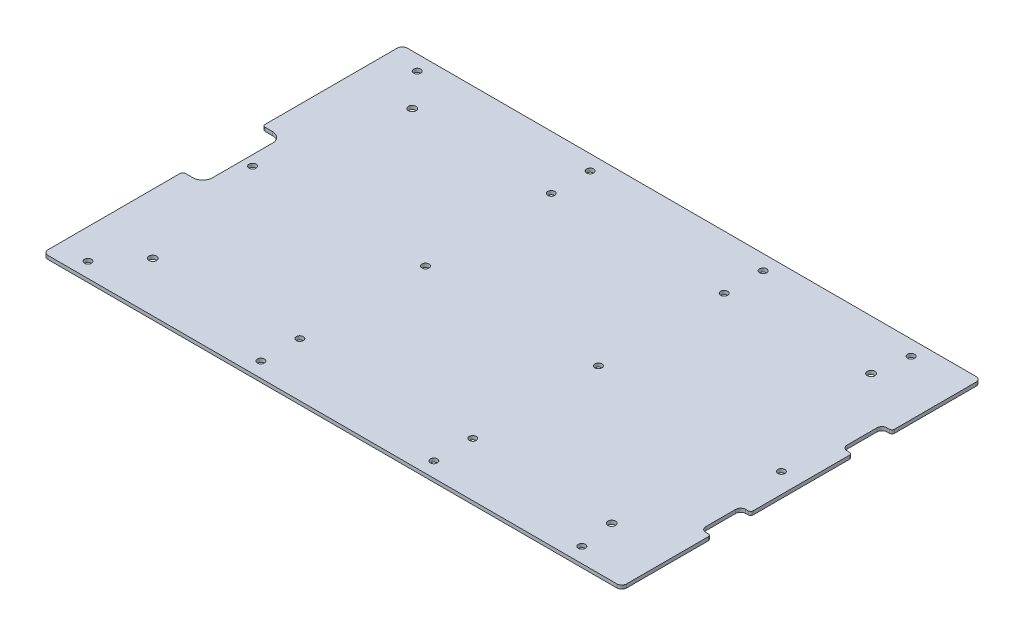
SolidWorks part; units mm, degrees
material "1060 Alloy"
ref_plane "Front" through (0, 0, 0) normal (0, 0, 1) x (1, 0, 0)
ref_plane "Top" through (0, 0, 0) normal (0, 1, 0) x (1, 0, 0)
ref_plane "Right" through (0, 0, 0) normal (1, 0, 0) x (0, 0, -1)
sketch "Sketch1" plane through (0, 0, 0) normal (0, 1, 0) x (1, 0, 0)
  line L0 (-55.0333, 0) -> (-165.1, 0) construction
  line L1 (-180.975, 114.3) -> (180.975, 114.3)
  line L2 (-184.15, 111.125) -> (-184.15, -111.125)
  line L3 (-180.975, -114.3) -> (180.975, -114.3)
  line L4 (184.15, 111.125) -> (184.15, -111.125)
  line L5 (-184.15, 114.3) -> (184.15, -114.3) construction
  line L6 (-184.15, -114.3) -> (184.15, 114.3) construction
  line L7 (-165.1, -104.775) -> (165.1, -104.775) construction
  line L8 (-165.1, -104.775) -> (-165.1, 104.775) construction
  line L9 (-165.1, 104.775) -> (165.1, 104.775) construction
  line L10 (165.1, -104.775) -> (165.1, 104.775) construction
  line L11 (-165.1, -104.775) -> (165.1, 104.775) construction
  line L12 (-165.1, 104.775) -> (165.1, -104.775) construction
  line L13 (-55.0333, -104.775) -> (55.0333, -104.775) construction
  line L14 (-55.0333, -104.775) -> (-55.0333, 104.775) construction
  line L15 (-55.0333, 104.775) -> (55.0333, 104.775) construction
  line L16 (55.0333, -104.775) -> (55.0333, 104.775) construction
  line L17 (-55.0333, -104.775) -> (55.0333, 104.775) construction
  line L18 (-55.0333, 104.775) -> (55.0333, -104.775) construction
  line L19 (55.0333, 0) -> (165.1, 0) construction
  line L20 (-55.0333, 0) -> (55.0333, 0) construction
  line L31 (-55.0291, 80.01) -> (55.0291, 80.01) construction
  line L32 (149.225, -104.775) -> (149.225, 104.775) construction
  line L33 (-55.0291, 80.01) -> (-55.0291, -80.01) construction
  line L34 (-55.0291, -80.01) -> (55.0291, -80.01) construction
  line L35 (55.0291, 80.01) -> (55.0291, -80.01) construction
  line L36 (-55.0291, 80.01) -> (55.0291, -80.01) construction
  line L37 (-55.0291, -80.01) -> (55.0291, 80.01) construction
  circle A0 centre (-165.1, 104.775) radius 2.2479
  circle A1 centre (-55.0333, 104.775) radius 2.2479
  circle A2 centre (55.0333, 104.775) radius 2.2479
  circle A3 centre (165.1, 104.775) radius 2.2479 construction
  circle A4 centre (165.1, -104.775) radius 2.2479 construction
  circle A5 centre (55.0333, -104.775) radius 2.2479
  circle A6 centre (-55.0333, -104.775) radius 2.2479
  circle A7 centre (-165.1, -104.775) radius 2.2479
  circle A12 centre (-55.0333, 0) radius 2.2479
  circle A13 centre (55.0333, 0) radius 2.2479
  arc A14 (184.15, 111.125) -> (180.975, 114.3) centre (180.975, 111.125) ccw
  arc A15 (184.15, -111.125) -> (180.975, -114.3) centre (180.975, -111.125) cw
  arc A16 (-180.975, -114.3) -> (-184.15, -111.125) centre (-180.975, -111.125) cw
  arc A17 (-180.975, 114.3) -> (-184.15, 111.125) centre (-180.975, 111.125) ccw
  circle A24 centre (149.225, -104.775) radius 2.2479
  circle A25 centre (149.225, 104.775) radius 2.2479
  circle A26 centre (55.0291, -80.01) radius 2.2479
  circle A27 centre (-55.0291, -80.01) radius 2.2479
  circle A28 centre (-55.0291, 80.01) radius 2.2479
  circle A29 centre (55.0291, 80.01) radius 2.2479
  circle A30 centre (171.45, 0) radius 2.2479
  circle A31 centre (-165.1, 0) radius 2.2479
  circle A32 centre (-146.05, 82.55) radius 2.4574 construction
  circle A33 centre (-146.05, 82.55) radius 2.4575
  circle A34 centre (146.05, 82.55) radius 2.4574 construction
  circle A35 centre (146.05, 82.55) radius 2.4575
  circle A36 centre (-146.05, -82.55) radius 2.4574 construction
  circle A37 centre (-146.05, -82.55) radius 2.4575
  circle A38 centre (146.05, -82.55) radius 2.4574 construction
  circle A39 centre (146.05, -82.55) radius 2.4575
  point P0 (0, 0)
  point P6 (0, 0)
  point P11 (0, 0)
  point P28 (0, 0)
  point P29 (0, 0)
  point P32 (0, 0)
  dimension "D5" = 4.4958
  dimension "D8" = 4.4958
  dimension "D11" = 3.175
  dimension "D10" = 12.7
  dimension "D12" = 19.05
  dimension "D13" = 110.0667
  dimension "D1" = 368.3
  dimension "D2" = 228.6
  dimension "D3" = 9.525
  dimension "D4" = 19.05
  dimension "D6" = 160.02
  dimension "D7" = 34.925
  dimension "D9" = 110.0582
extrude "Boss-Extrude1" add sketch "Sketch1" along normal blind 2.286
sketch "Sketch2" plane through (0, 0, 0) normal (0, -1, 0) x (1, 0, 0)
  line L5 (184.15, 111.125) -> (184.15, -111.125) construction
  line L6 (184.15, 57.658) -> (180.975, 57.658)
  line L7 (184.15, 57.658) -> (184.15, 32.258)
  line L8 (184.15, 32.258) -> (180.975, 32.258)
  line L9 (177.8, 54.483) -> (177.8, 35.433)
  line L10 (-184.15, 0) -> (184.15, 0) construction
  line L11 (-184.15, -111.125) -> (-184.15, 111.125) construction
  line L13 (177.8, 44.958) -> (184.15, 44.958) construction
  line L14 (184.15, -32.258) -> (180.975, -32.258)
  line L15 (184.15, -57.658) -> (184.15, -32.258)
  line L16 (177.8, -54.483) -> (177.8, -35.433)
  line L17 (184.15, -57.658) -> (180.975, -57.658)
  line L19 (-184.15, 25.4) -> (-177.8, 25.4)
  line L20 (-184.15, 25.4) -> (-184.15, -25.4)
  line L21 (-184.15, -25.4) -> (-177.8, -25.4)
  line L22 (-171.45, 19.05) -> (-171.45, -19.05)
  arc A0 (180.975, -57.658) -> (177.8, -54.483) centre (180.975, -54.483) cw
  arc A1 (177.8, -35.433) -> (180.975, -32.258) centre (180.975, -35.433) cw
  arc A2 (177.8, 35.433) -> (180.975, 32.258) centre (180.975, 35.433) ccw
  arc A3 (177.8, 54.483) -> (180.975, 57.658) centre (180.975, 54.483) cw
  arc A4 (-171.45, -19.05) -> (-177.8, -25.4) centre (-177.8, -19.05) cw
  arc A5 (-171.45, 19.05) -> (-177.8, 25.4) centre (-177.8, 19.05) ccw
  point P20 (177.8, -57.658)
  point P23 (177.8, -32.258)
  point P26 (177.8, 32.258)
  point P29 (177.8, 57.658)
  point P38 (-171.45, 25.4)
  dimension "D4" = 3.175
  dimension "D7" = 6.35
  dimension "D1" = 25.4
  dimension "D2" = 44.958
  dimension "D3" = 6.35
  dimension "D5" = 50.8
  dimension "D6" = 12.7
extrude "Cut-Extrude1" cut sketch "Sketch2" against normal through all
fillet "Fillet1" radius 1.5875 6 edges at (184.15, 1.143, -57.658) (184.15, 1.143, -32.258) (184.15, 1.143, 32.258) (184.15, 1.143, 57.658) (-184.15, 1.143, -25.4) (-184.15, 1.143, 25.4)
sketch "Sketch3" plane through (0, 2.286, 0) normal (0, 1, 0) x (1, 0, 0)
  line L0 (-198.0256, -111.0509) -> (-198.0256, 117.5491)
  line L1 (204.2781, -126.2696) -> (-1014.9219, -126.2696)
  line L2 (204.2781, -126.2696) -> (204.2781, 1092.9304)
  line L3 (204.2781, 1092.9304) -> (-1014.9219, 1092.9304)
  line L4 (-1014.9219, -126.2696) -> (-1014.9219, 1092.9304)
  line L5 (182.9744, -111.0509) -> (-185.3256, -111.0509)
  line L6 (182.9744, -111.0509) -> (182.9744, 117.5491)
  line L7 (182.9744, 117.5491) -> (-185.3256, 117.5491)
  line L8 (-185.3256, -111.0509) -> (-185.3256, 117.5491)
  line L9 (-198.0256, -111.0509) -> (-566.3256, -111.0509)
  line L10 (-566.3256, -111.0509) -> (-566.3256, 117.5491)
  line L11 (-198.0256, 117.5491) -> (-566.3256, 117.5491)
  line L12 (-579.0256, -111.0509) -> (-579.0256, 117.5491)
  line L13 (-579.0256, -111.0509) -> (-947.3256, -111.0509)
  line L14 (-947.3256, -111.0509) -> (-947.3256, 117.5491)
  line L15 (-579.0256, 117.5491) -> (-947.3256, 117.5491)
  line L16 (-198.0256, 130.2491) -> (-198.0256, 358.8491)
  line L17 (-198.0256, 130.2491) -> (-566.3256, 130.2491)
  line L18 (-566.3256, 130.2491) -> (-566.3256, 358.8491)
  line L19 (-198.0256, 358.8491) -> (-566.3256, 358.8491)
  line L20 (-579.0256, 130.2491) -> (-579.0256, 358.8491)
  line L21 (-579.0256, 130.2491) -> (-947.3256, 130.2491)
  line L22 (-947.3256, 130.2491) -> (-947.3256, 358.8491)
  line L23 (-579.0256, 358.8491) -> (-947.3256, 358.8491)
  line L24 (-198.0256, 371.5491) -> (-198.0256, 600.1491)
  line L25 (-198.0256, 371.5491) -> (-566.3256, 371.5491)
  line L26 (-566.3256, 371.5491) -> (-566.3256, 600.1491)
  line L27 (-198.0256, 600.1491) -> (-566.3256, 600.1491)
  line L28 (-579.0256, 371.5491) -> (-579.0256, 600.1491)
  line L29 (-579.0256, 371.5491) -> (-947.3256, 371.5491)
  line L30 (-947.3256, 371.5491) -> (-947.3256, 600.1491)
  line L31 (-579.0256, 600.1491) -> (-947.3256, 600.1491)
  line L32 (-198.0256, 612.8491) -> (-198.0256, 841.4491)
  line L33 (-198.0256, 612.8491) -> (-566.3256, 612.8491)
  line L34 (-566.3256, 612.8491) -> (-566.3256, 841.4491)
  line L35 (-198.0256, 841.4491) -> (-566.3256, 841.4491)
  line L36 (-579.0256, 612.8491) -> (-579.0256, 841.4491)
  line L37 (-579.0256, 612.8491) -> (-947.3256, 612.8491)
  line L38 (-947.3256, 612.8491) -> (-947.3256, 841.4491)
  line L39 (-579.0256, 841.4491) -> (-947.3256, 841.4491)
  line L40 (-198.0256, 854.1491) -> (-198.0256, 1082.7491)
  line L41 (-198.0256, 854.1491) -> (-566.3256, 854.1491)
  line L42 (-566.3256, 854.1491) -> (-566.3256, 1082.7491)
  line L43 (-198.0256, 1082.7491) -> (-566.3256, 1082.7491)
  line L44 (-579.0256, 854.1491) -> (-579.0256, 1082.7491)
  line L45 (-579.0256, 854.1491) -> (-947.3256, 854.1491)
  line L46 (-947.3256, 854.1491) -> (-947.3256, 1082.7491)
  line L47 (-579.0256, 1082.7491) -> (-947.3256, 1082.7491)
  line L48 (182.9744, 130.2491) -> (182.9744, 358.8491)
  line L49 (182.9744, 130.2491) -> (-185.3256, 130.2491)
  line L50 (-185.3256, 130.2491) -> (-185.3256, 358.8491)
  line L51 (182.9744, 358.8491) -> (-185.3256, 358.8491)
  line L52 (182.9744, 371.5491) -> (182.9744, 600.1491)
  line L53 (182.9744, 371.5491) -> (-185.3256, 371.5491)
  line L54 (-185.3256, 371.5491) -> (-185.3256, 600.1491)
  line L55 (182.9744, 600.1491) -> (-185.3256, 600.1491)
  line L56 (182.9744, 612.8491) -> (182.9744, 841.4491)
  line L57 (182.9744, 612.8491) -> (-185.3256, 612.8491)
  line L58 (-185.3256, 612.8491) -> (-185.3256, 841.4491)
  line L59 (182.9744, 841.4491) -> (-185.3256, 841.4491)
  line L60 (182.9744, 854.1491) -> (182.9744, 1082.7491)
  line L61 (182.9744, 854.1491) -> (-185.3256, 854.1491)
  line L62 (-185.3256, 854.1491) -> (-185.3256, 1082.7491)
  line L63 (182.9744, 1082.7491) -> (-185.3256, 1082.7491)
  dimension "D1" = 1219.2
  dimension "D2" = 1219.2
  dimension "D3" = 368.3
  dimension "D4" = 228.6
  dimension "D5" = 3
  dimension "D6" = 5
